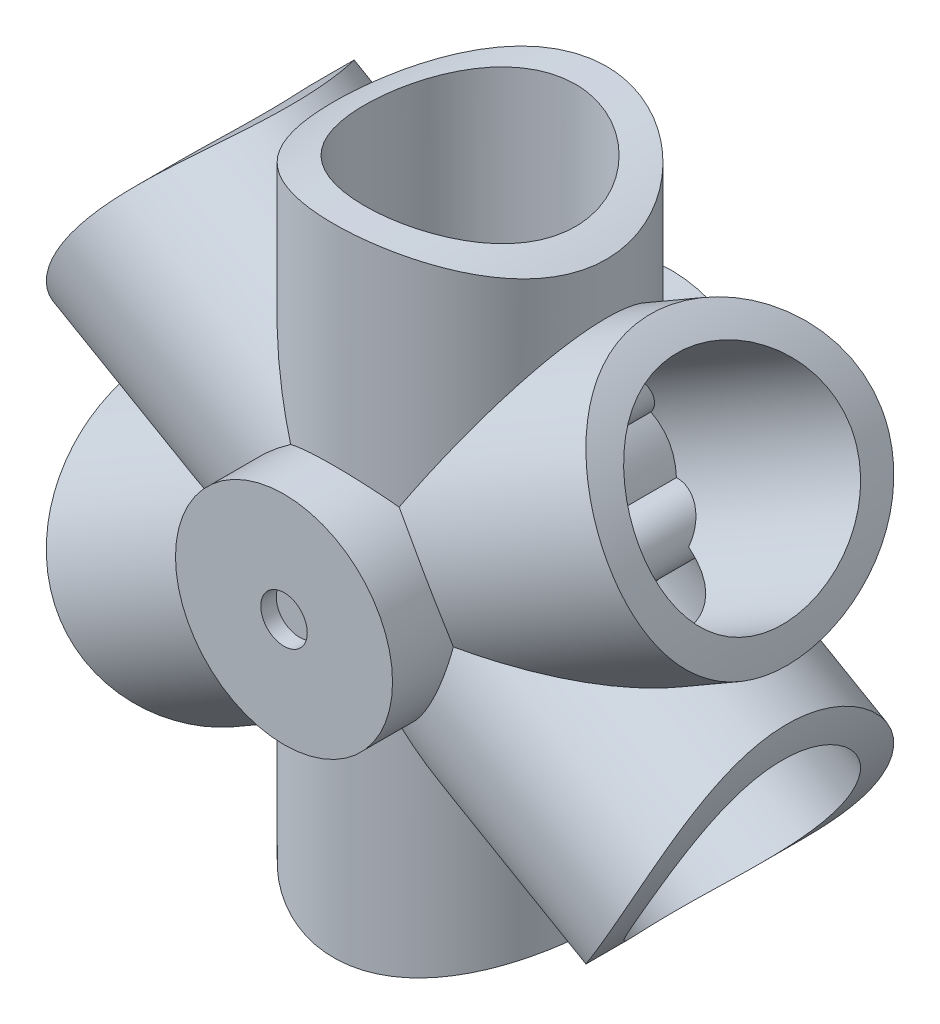
SolidWorks part; units mm, degrees
ref_plane "Front Plane" through (0, 0, 0) normal (0, 0, 1) x (1, 0, 0)
ref_plane "Top Plane" through (0, 0, 0) normal (0, 1, 0) x (1, 0, 0)
ref_plane "Right Plane" through (0, 0, 0) normal (1, 0, 0) x (0, 0, -1)
sketch "Sketch1" plane through (0, 0, 0) normal (0, 1, 0) x (1, 0, 0)
  circle A0 centre (0, 0) radius 11.176
  circle A1 centre (0, 0) radius 8.636
  dimension "D1" = 22.352
  dimension "D2" = 17.272
extrude "Boss-Extrude1" add sketch "Sketch1" along normal blind 20.32
sketch "Sketch2" plane through (0, 0, 0) normal (0, 0, 1) x (1, 0, 0)
  line L0 (11.176, 20.32) -> (-11.176, 20.32) construction
  line L1 (-8.636, 20.32) -> (-11.176, 20.32)
  line L2 (8.4632, 20.32) -> (11.0032, 20.32)
  line L3 (0, 20.32) -> (0, 38.4954) construction
  arc A2 (8.4632, 20.32) -> (-8.636, 20.32) centre (-0.0864, 7.6039) ccw
  arc A3 (11.0032, 20.32) -> (-11.176, 20.32) centre (-0.0864, 7.6039) ccw
revolve "Revolve1" add sketch "Sketch2" angle 360 about L3 region at (-9.906, 20.5457, 0)
ref_plane "Plane1" through (0, 27.94, 0) normal (0, -1, 0) x (-1, 0, 0)
sketch "Sketch3" plane through (0, 27.94, 0) normal (0, -1, 0) x (-1, 0, 0)
  line L0 (0, 11.9871) -> (0, -12.3331)
pattern_circular "CirPattern1" count 6 over 360 about axis through (0, 27.94, -11.9871) along (0, 0, 1) of bodies 103
sketch "Sketch4" plane through (0, 0, 0) normal (0, 0, 1) x (1, 0, 0)
  circle A0 centre (0, 27.94) radius 8.89
extrude "Boss-Extrude2" add sketch "Sketch4" along normal blind 15.24 and the other way blind 16.51
sketch "Sketch5" plane through (0, 0, 15.24) normal (0, 0, 1) x (1, 0, 0)
  circle A0 centre (0, 27.94) radius 26.035
  circle A1 centre (0, 27.94) radius 34.3456
  dimension "D1" = 52.07
extrude "Cut-Extrude1" cut sketch "Sketch5" against normal through all
sketch "Sketch8" plane through (0, 0, 0) normal (0, 1, 0) x (1, 0, 0)
  circle A0 centre (0, 0) radius 8.636
extrude "Cut-Extrude2" cut sketch "Sketch8" along normal up to surface (19.05 mm away) up to face at (0, 19.067, 0)
pattern_circular "CirPattern2" count 6 over 360 about axis through (0, 27.94, -16.51) along (0, 0, 1) of "Cut-Extrude2"
sketch "Sketch9" plane through (0, 0, -16.51) normal (0, 0, -1) x (-1, 0, 0)
  line L0 (-159.3608, -65.013) -> (-26.0275, -65.013) construction
  line L1 (-5.3001, 25.0893) -> (-5.3001, 24.6378)
  line L2 (-5.3001, 32.5511) -> (5.1143, 32.5511)
  line L3 (-6.5701, 31.2811) -> (-6.5701, 23.7722)
  line L4 (-5.3001, 22.5022) -> (5.1143, 22.5022)
  line L5 (6.3843, 31.2811) -> (6.3843, 23.7722)
  line L6 (-4.9342, 31.6555) -> (4.7922, 31.6555)
  line L7 (-5.6962, 30.8935) -> (-5.6962, 24.1162)
  line L8 (-4.9342, 23.3542) -> (4.7922, 23.3542)
  line L9 (5.5542, 30.8935) -> (5.5542, 24.1162)
  line L10 (-5.3001, 24.6378) -> (-3.6843, 24.6378)
  line L11 (-3.6843, 24.6378) -> (-3.6843, 25.0893)
  line L12 (-3.6843, 25.0893) -> (-4.0153, 25.0893)
  line L13 (-4.0153, 25.0893) -> (-2.7662, 29.1074)
  line L14 (-2.7662, 29.1074) -> (-0.7496, 27.3015)
  line L15 (-0.7496, 27.3015) -> (-0.7496, 24.8635)
  line L16 (-0.7496, 24.8635) -> (-1.5021, 24.8635)
  line L17 (-1.5021, 24.8635) -> (-1.5021, 24.4572)
  line L18 (-1.5021, 24.4572) -> (-0.2379, 24.4572)
  line L19 (-0.2379, 24.4572) -> (-0.2379, 31.2811)
  line L20 (-0.2379, 31.2811) -> (-1.7579, 31.2811)
  line L21 (-1.7579, 31.2811) -> (-1.7579, 30.7478)
  line L22 (-1.7579, 30.7478) -> (-0.7496, 30.7478)
  line L23 (-0.7496, 30.7478) -> (-0.7496, 28.656)
  line L24 (-0.7496, 28.656) -> (-2.6007, 30.507)
  line L25 (-2.6007, 30.507) -> (-4.3163, 25.0893)
  line L26 (-4.3163, 25.0893) -> (-5.3001, 25.0893)
  line L27 (-0.071, 31.6555) -> (-0.071, 23.3542) construction
  line L28 (2.4587, 30.507) -> (4.1743, 25.0893)
  line L29 (0.6076, 28.656) -> (2.4587, 30.507)
  line L30 (0.6076, 30.7478) -> (0.6076, 28.656)
  line L31 (1.6159, 30.7478) -> (0.6076, 30.7478)
  line L32 (1.6159, 31.2811) -> (1.6159, 30.7478)
  line L33 (0.0959, 31.2811) -> (1.6159, 31.2811)
  line L34 (0.0959, 24.4572) -> (0.0959, 31.2811)
  line L35 (1.3601, 24.4572) -> (0.0959, 24.4572)
  line L36 (1.3601, 24.8635) -> (1.3601, 24.4572)
  line L37 (0.6076, 24.8635) -> (1.3601, 24.8635)
  line L38 (0.6076, 27.3015) -> (0.6076, 24.8635)
  line L39 (2.6242, 29.1074) -> (0.6076, 27.3015)
  line L40 (3.8733, 25.0893) -> (2.6242, 29.1074)
  line L41 (3.5422, 25.0893) -> (3.8733, 25.0893)
  line L42 (3.5422, 24.6378) -> (3.5422, 25.0893)
  line L43 (5.158, 24.6378) -> (3.5422, 24.6378)
  line L44 (5.158, 25.0893) -> (5.158, 24.6378)
  line L45 (4.1743, 25.0893) -> (5.158, 25.0893)
  line L47 (-5.3001, 24.3067) -> (5.1143, 24.3067)
  line L48 (-5.3001, 24.3067) -> (-5.3001, 23.8703)
  line L49 (-5.3001, 23.8703) -> (5.1143, 23.8703)
  line L50 (5.1143, 24.3067) -> (5.1143, 23.8703)
  arc A0 (5.1143, 32.5511) -> (6.3843, 31.2811) centre (5.1143, 31.2811) cw
  arc A1 (5.1143, 22.5022) -> (6.3843, 23.7722) centre (5.1143, 23.7722) ccw
  arc A2 (-6.5701, 23.7722) -> (-5.3001, 22.5022) centre (-5.3001, 23.7722) ccw
  arc A3 (-5.3001, 32.5511) -> (-6.5701, 31.2811) centre (-5.3001, 31.2811) ccw
  arc A4 (4.7922, 31.6555) -> (5.5542, 30.8935) centre (4.7922, 30.8935) cw
  arc A5 (4.7922, 23.3542) -> (5.5542, 24.1162) centre (4.7922, 24.1162) ccw
  arc A6 (-5.6962, 24.1162) -> (-4.9342, 23.3542) centre (-4.9342, 24.1162) ccw
  arc A7 (-4.9342, 31.6555) -> (-5.6962, 30.8935) centre (-4.9342, 30.8935) ccw
  dimension "D1" = 1.27
  dimension "D2" = 0.762
extrude "Cut-Extrude3" cut sketch "Sketch9" against normal blind 1.27 contours L25 L26 L1 L10 L11 L12 L13 L14 L15 L16 L17 L18 L19 L20 L21 L22 L23 L24 | L45 L28 L29 L30 L31 L32 L33 L34 L35 L36 L37 L38 L39 L40 L41 L42 L43 L44 | L2 A3 L3 A2 L4 A1 L5 A0 A7 L6 A4 L9 A5 L8 A6 L7 region at (4.8082, 25.0043, -16.51) region at (0.0929, 32.3872, -16.51) region at (-3.2355, 27.7725, -16.51)
sketch "Sketch10" plane through (0, 0, 15.24) normal (0, 0, 1) x (1, 0, 0)
  circle A0 centre (0, 27.94) radius 1.905
  arc A1 (-4.445, 35.639) -> (-8.89, 27.94) centre (0, 27.94) ccw construction
  dimension "D1" = 3.81
extrude "Cut-Extrude4" cut sketch "Sketch10" against normal blind 1.27 contours A0
sketch "Sketch12" plane through (0, 0, 0) normal (0, 0, 1) x (1, 0, 0)
  line L0 (-8.89, 27.94) -> (-17.272, 27.94) construction
  circle A0 centre (-8.89, 27.94) radius 2.54
  circle A1 centre (0, 27.94) radius 8.89 construction
  dimension "D1" = 5.08
extrude "Boss-Extrude3" add sketch "Sketch12" along normal up to next and the other way up to next
pattern_circular "CirPattern3" count 6 over 360 about axis through (0, 27.94, -16.51) along (0, 0, 1) of "Boss-Extrude3"
